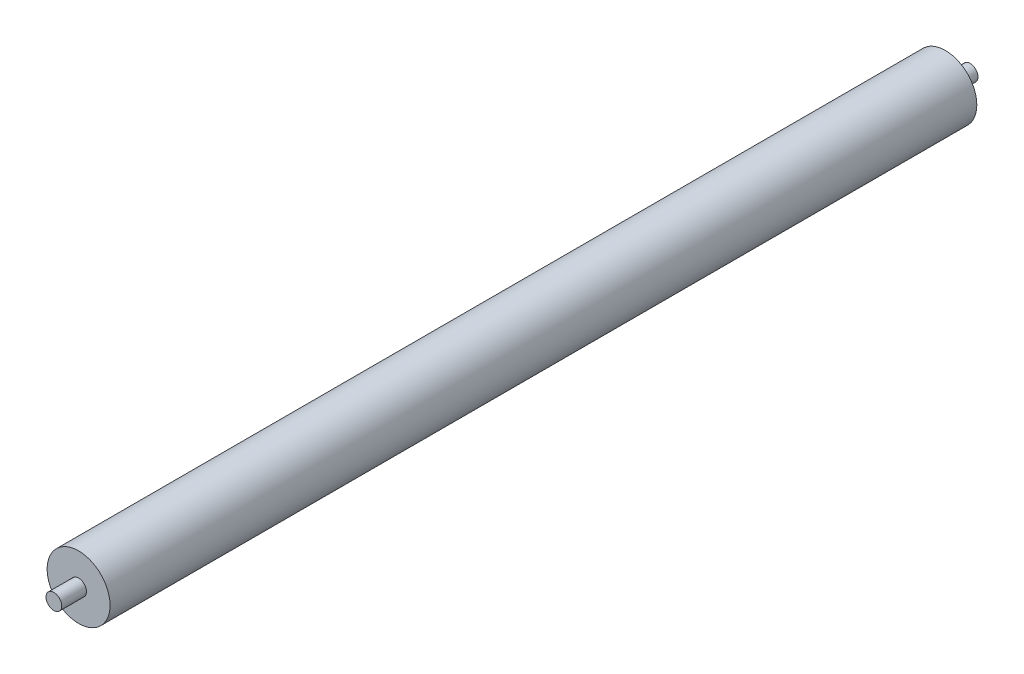
SolidWorks part; units mm, degrees
ref_plane "Alzado" through (0, 0, 0) normal (0, 0, 1) x (1, 0, 0)
ref_plane "Planta" through (0, 0, 0) normal (0, 1, 0) x (1, 0, 0)
ref_plane "Vista lateral" through (0, 0, 0) normal (1, 0, 0) x (0, 0, -1)
sketch "Sketch1" plane through (0, 0, 0) normal (0, 0, 1) x (1, 0, 0)
  circle A0 centre (0, 0) radius 25.4
  dimension "D1" = 50.8
extrude "Boss-Extrude1" add sketch "Sketch1" along normal mid plane 700
sketch "Sketch2" plane through (0, 0, 0) normal (0, 0, 1) x (1, 0, 0)
  circle A0 centre (0, 0) radius 6.35
  dimension "D1" = 12.7
extrude "Boss-Extrude2" add sketch "Sketch2" along normal mid plane 740 contours A0
ref_axis "Axis1" through (0, 0, -407) along (0, 0, 1)
